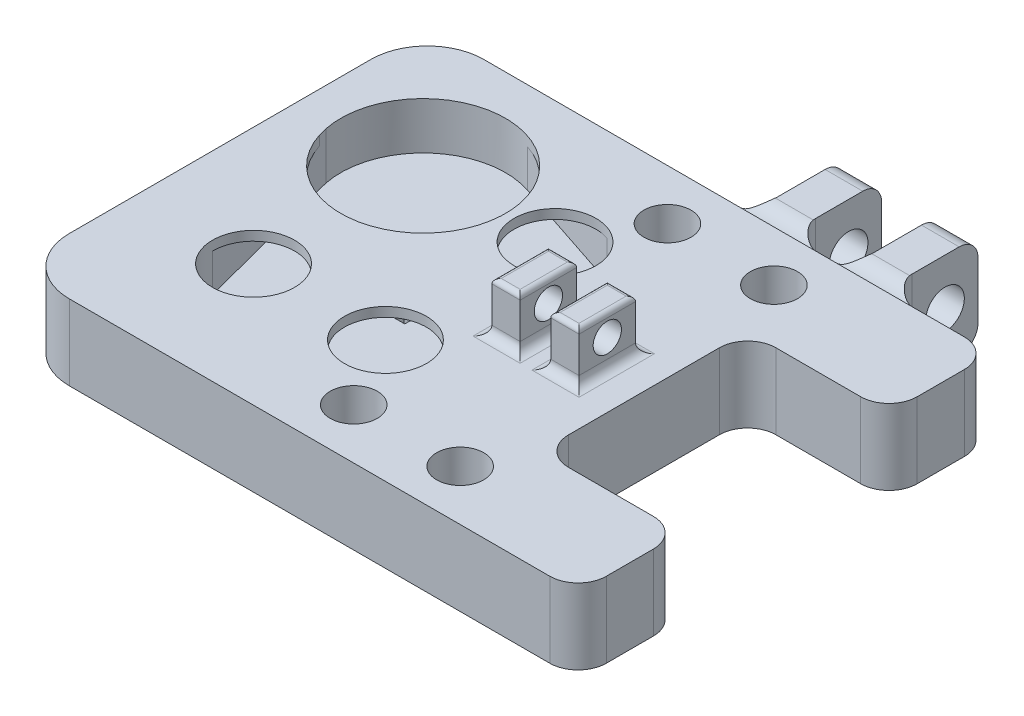
SolidWorks part; units mm, degrees
ref_plane "Front Plane" through (0, 0, 0) normal (0, 0, 1) x (1, 0, 0)
ref_plane "Top Plane" through (0, 0, 0) normal (0, 1, 0) x (1, 0, 0)
ref_plane "Right Plane" through (0, 0, 0) normal (1, 0, 0) x (0, 0, -1)
sketch "Sketch2" plane through (0, 0, 0) normal (0, 1, 0) x (1, 0, 0)
  line L1 (-14.4231, 13.5577) -> (30.5769, 13.5577)
  line L2 (-14.4231, 13.5577) -> (-14.4231, -8.4423)
  line L3 (-14.4231, -8.4423) -> (30.5769, -8.4423)
  line L4 (30.5769, 13.5577) -> (30.5769, -8.4423)
  dimension "D1" = 45
  dimension "D2" = 22
extrude "Boss-Extrude1" add sketch "Sketch2" along normal blind 8
sketch "Sketch3" plane through (0, 0, 0) normal (0, -1, 0) x (1, 0, 0)
  line L0 (30.5769, 8.4423) -> (30.5769, -13.5577) construction
  line L1 (23.5769, -4.0677) -> (3.5769, -4.0677)
  line L2 (23.5769, -4.0677) -> (23.5769, -1.0477)
  line L3 (23.5769, -1.0477) -> (3.5769, -1.0477)
  line L4 (3.5769, -4.0677) -> (3.5769, -1.0477)
  line L5 (-14.4231, -2.5577) -> (30.5769, -2.5577) construction
  line L6 (-14.4231, -13.5577) -> (-14.4231, 8.4423) construction
  dimension "D1" = 20
  dimension "D2" = 7
  dimension "D3" = 3.02
  dimension "D4" = 1.51
extrude "Cut-Extrude1" cut sketch "Sketch3" against normal blind 2
sketch "Sketch4" plane through (0, 0, 0) normal (0, -1, 0) x (1, 0, 0)
  line L0 (3.5769, -1.0477) -> (3.5769, -4.0677) construction
  line L1 (3.5769, -7.5577) -> (-6.4231, -7.5577)
  line L2 (3.5769, -7.5577) -> (3.5769, 2.4423)
  line L3 (3.5769, 2.4423) -> (-6.4231, 2.4423)
  line L4 (-6.4231, -7.5577) -> (-6.4231, -2.5577)
  line L5 (23.5769, -2.5577) -> (-14.4231, -2.5577) construction
  line L7 (23.5769, -4.0677) -> (23.5769, -1.0477) construction
  line L8 (-14.4231, -13.5577) -> (-14.4231, 8.4423) construction
  line L9 (-6.4231, -2.5577) -> (-6.4231, 2.4423)
  dimension "D1" = 10
  dimension "D2" = 10
extrude "Cut-Extrude2" [suppressed] cut sketch "Sketch4" against normal blind 5
sketch "Sketch11" plane through (0, 0, 0) normal (0, -1, 0) x (1, 0, 0)
  circle A0 centre (24.8884, -2.5577) radius 2
  dimension "D1" = 4
extrude "Cut-Extrude4" cut sketch "Sketch11" against normal up to surface (2 mm away) up to face at (13.5769, 2, -2.5577)
sketch "Sketch18" plane through (0, 0, 0) normal (0, -1, 0) x (1, 0, 0)
  line L0 (22.0769, 1.6923) -> (22.0769, -8.4603) construction
  line L4 (30.5769, 8.4423) -> (30.5769, -13.5577) construction
  line L5 (-14.4231, -2.5577) -> (42.1382, -2.5577) construction
  line L6 (-14.4231, -13.5577) -> (-14.4231, 8.4423) construction
  line L7 (2.0769, 1.6923) -> (2.0769, -2.5577) construction
  line L8 (3.3269, -6.8077) -> (3.3269, -2.5577) construction
  circle A0 centre (22.0769, 1.6923) radius 0.6
  circle A1 centre (19.5769, 1.6923) radius 0.6
  circle A2 centre (17.0769, 1.6923) radius 0.6
  circle A3 centre (14.5769, 1.6923) radius 0.6
  circle A4 centre (12.0769, 1.6923) radius 0.6
  circle A5 centre (9.5769, 1.6923) radius 0.6
  circle A6 centre (7.0769, 1.6923) radius 0.6
  circle A7 centre (4.5769, 1.6923) radius 0.6
  circle A8 centre (2.0769, 1.6923) radius 0.6
  circle A9 centre (20.8269, -6.8077) radius 0.6
  circle A10 centre (18.3269, -6.8077) radius 0.6
  circle A11 centre (15.8269, -6.8077) radius 0.6
  circle A12 centre (13.3269, -6.8077) radius 0.6
  circle A13 centre (10.8269, -6.8077) radius 0.6
  circle A14 centre (8.3269, -6.8077) radius 0.6
  circle A15 centre (5.8269, -6.8077) radius 0.6
  circle A16 centre (3.3269, -6.8077) radius 0.6
  dimension "D2" = 1.2
  dimension "D7" = 1.2
  dimension "D3" = 8.5
  dimension "D5" = 1.25
  dimension "D6" = 8.5
  dimension "D1" = 9
  dimension "D8" = 8
sketch "Sketch19" plane through (0, 0, 0) normal (0, -1, 0) x (1, 0, 0)
  line L0 (3.5769, -4.0677) -> (23.5769, -4.0677) construction
  line L5 (3.5769, -1.0477) -> (6.6946, -1.0477)
  line L6 (3.5769, -1.0477) -> (3.5769, -4.0677)
  line L7 (3.5769, -4.0677) -> (6.6946, -4.0677)
  line L8 (6.6946, -1.0477) -> (6.6946, -4.0677)
  dimension "D1" = 3.1177
extrude "Cut-Extrude5" cut sketch "Sketch19" against normal blind 3
sketch "Sketch29" plane through (0, 8, 0) normal (0, 1, 0) x (1, 0, 0)
  line L1 (-14.4231, 13.5577) -> (25.5769, 13.5577)
  line L2 (-14.4231, 13.5577) -> (-14.4231, 24.5577)
  line L3 (-14.4231, 24.5577) -> (25.5769, 24.5577)
  line L4 (25.5769, 13.5577) -> (25.5769, 24.5577)
  line L5 (-14.4231, -8.4423) -> (25.5769, -8.4423)
  line L6 (-14.4231, -8.4423) -> (-14.4231, -19.4423)
  line L7 (-14.4231, -19.4423) -> (25.5769, -19.4423)
  line L8 (25.5769, -8.4423) -> (25.5769, -19.4423)
  dimension "D1" = 40
  dimension "D2" = 11
extrude "Boss-Extrude6" add sketch "Sketch29" against normal up to surface (8 mm away) up to face at (14.4048, 0, -2.5577)
sketch "Sketch21" plane through (0, 3, 0) normal (0, -1, 0) x (1, 0, 0)
  line L0 (3.5769, -2.5577) -> (6.6946, -2.5577) construction
  line L1 (3.5769, -1.0477) -> (3.5769, -4.0677) construction
  line L2 (6.6946, -4.0677) -> (6.6946, -1.0477) construction
  line L3 (5.1358, -1.0477) -> (5.1358, -4.0677) construction
  line L4 (23.5769, -1.0477) -> (3.5769, -1.0477) construction
  line L5 (3.5769, -4.0677) -> (23.5769, -4.0677) construction
  line L6 (19.1358, 15.4423) -> (19.1358, -20.5577)
  line L7 (-10.8642, 15.4423) -> (19.1358, 15.4423)
  line L8 (-10.8642, 15.4423) -> (-10.8642, -20.5577)
  line L9 (-10.8642, -20.5577) -> (19.1358, -20.5577)
  point P12 (5.1358, -2.5577)
  dimension "D1" = 30
  dimension "D2" = 36
  dimension "D3" = 16
extrude "Cut-Extrude8" cut sketch "Sketch21" against normal up to surface (5 mm away) up to face at (16.8269, 8, -2.5577)
sketch "Sketch24" plane through (0, 8, 0) normal (0, 1, 0) x (1, 0, 0)
  line L0 (5.1358, 20.5577) -> (5.1358, -15.4423) construction
  line L1 (-10.8642, -15.4423) -> (-10.8642, 20.5577) construction
  line L3 (-10.8642, 2.5577) -> (21.1358, 2.5577) construction
  line L6 (-1.8642, 11.5577) -> (-1.8642, -6.4423) construction
  line L7 (-10.8642, 20.5577) -> (19.1358, 20.5577)
  line L8 (-10.8642, 20.5577) -> (-10.8642, -15.4423)
  line L9 (-10.8642, -15.4423) -> (19.1358, -15.4423)
  line L10 (19.1358, 20.5577) -> (19.1358, -15.4423)
  line L11 (12.1358, 11.5577) -> (12.1358, -6.4423) construction
  line L13 (12.1358, -6.4423) -> (-1.8642, -6.4423) construction
  line L14 (19.1358, 20.5577) -> (19.1358, -15.4423) construction
  circle A1 centre (12.1358, 11.5577) radius 4.35
  circle A11 centre (-1.8642, 11.5577) radius 8.75
  circle A12 centre (12.1358, -6.4423) radius 4.35
  circle A13 centre (-1.8642, -6.4423) radius 4.35
  point P29 (5.1358, 2.5577)
  dimension "D1" = 8.7
  dimension "D4" = 17.5
  dimension "D2" = 9
  dimension "D3" = 7
  dimension "D5" = 7
  dimension "D6" = 9
  dimension "D7" = 9
  dimension "D8" = 16
extrude "Boss-Extrude3" add sketch "Sketch24" against normal blind 1
sketch "Sketch25" plane through (0, 8, 0) normal (0, 1, 0) x (1, 0, 0)
  line L0 (22.0569, 10.0577) -> (22.0569, -4.9423) construction
  line L1 (20.4319, -0.4423) -> (17.4319, -0.4423)
  line L2 (26.6819, -0.4423) -> (23.6819, -0.4423)
  line L3 (26.6819, -0.4423) -> (26.6819, 5.5577)
  line L4 (26.6819, 5.5577) -> (23.6819, 5.5577)
  line L5 (23.6819, -0.4423) -> (23.6819, 5.5577)
  line L6 (26.6819, -0.4423) -> (23.6819, 5.5577) construction
  line L7 (26.6819, 5.5577) -> (23.6819, -0.4423) construction
  line L8 (20.4319, -0.4423) -> (20.4319, 5.5577)
  line L9 (20.4319, 5.5577) -> (17.4319, 5.5577)
  line L10 (17.4319, -0.4423) -> (17.4319, 5.5577)
  line L11 (20.4319, -0.4423) -> (17.4319, 5.5577) construction
  line L12 (20.4319, 5.5577) -> (17.4319, -0.4423) construction
  line L13 (-14.4231, 2.5577) -> (30.5769, 2.5577) construction
  line L14 (-14.4231, 24.5577) -> (-14.4231, -19.4423) construction
  line L15 (30.5769, -8.4423) -> (30.5769, 13.5577) construction
  circle A0 centre (22.0569, 2.5577) radius 6.2555
  circle A1 centre (22.0569, 2.5577) radius 5.8
  point P6 (22.0569, 2.5577)
  point P7 (25.1819, 2.5577)
  point P16 (18.9319, 2.5577)
  dimension "D1" = 15
  dimension "D2" = 3
  dimension "D3" = 6
  dimension "D4" = 3.125
  dimension "D5" = 3.125
  dimension "D6" = 6
  dimension "D7" = 3
  dimension "D8" = 8.52
extrude "Boss-Extrude4" add sketch "Sketch25" along normal blind 5.3 contours L10 L1 L8 L9 | L5 L2 L3 L4 region at (18.9319, 8, -2.5577) region at (25.1819, 8, -2.5577)
sketch "Sketch26" plane through (26.6819, 0, 0) normal (1, 0, 0) x (0, 0, -1)
  line L0 (2.5577, 13.3) -> (2.5577, 8) construction
  line L1 (-0.4423, 13.3) -> (5.5577, 13.3) construction
  line L2 (-8.4423, 8) -> (13.5577, 8) construction
  line L3 (-0.4423, 8) -> (5.5577, 8) construction
  circle A0 centre (2.5577, 11) radius 1.5
  dimension "D1" = 3
  dimension "D2" = 3
extrude "Cut-Extrude9" cut sketch "Sketch26" against normal up to surface (9.25 mm away) up to face at (17.4319, 10.65, -2.5577)
fillet "Fillet2" radius 1 8 edges at (25.1819, 8, -5.5577) (18.9319, 8, -5.5577) (23.6819, 8, -2.5577) (17.4319, 8, -2.5577) (26.6819, 8, -2.5577) (25.1819, 8, 0.4423) (18.9319, 8, 0.4423) (20.4319, 8, -2.5577)
fillet "Fillet3" radius 0.5 8 edges at (18.9319, 13.3, 0.4423) (20.4319, 13.3, -2.5577) (17.4319, 13.3, -2.5577) (18.9319, 13.3, -5.5577) (25.1819, 13.3, -5.5577) (25.1819, 13.3, 0.4423) (23.6819, 13.3, -2.5577) (26.6819, 13.3, -2.5577)
sketch "Sketch27" plane through (0, 8, 0) normal (0, 1, 0) x (1, 0, 0)
  line L0 (30.5769, 13.5577) -> (25.5769, 13.5577) construction
  line L1 (25.5769, 13.5577) -> (45.5769, 13.5577)
  line L2 (25.5769, 13.5577) -> (25.5769, 24.5577)
  line L3 (25.5769, 24.5577) -> (45.5769, 24.5577)
  line L4 (45.5769, 13.5577) -> (45.5769, 24.5577)
  line L5 (25.5769, 13.5577) -> (25.5769, 24.5577) construction
  dimension "D1" = 20
  dimension "D2" = 11
extrude "Boss-Extrude5" add sketch "Sketch27" against normal up to surface (8 mm away) up to face at (14.4048, 0, -2.5577)
sketch "Sketch28" plane through (0, 8, 0) normal (0, 1, 0) x (1, 0, 0)
  line L0 (16.4169, 19.2077) -> (27.7169, 19.2077) construction
  line L1 (30.5769, -8.4423) -> (30.5769, 13.5577) construction
  line L4 (-14.4231, 24.5577) -> (-14.4231, -19.4423) construction
  circle A0 centre (16.4169, 19.2077) radius 2.5
  circle A1 centre (27.7169, 19.2077) radius 2.5
  point P2 (-14.4231, 2.5577)
  dimension "D1" = 11.3
  dimension "D2" = 5
  dimension "D3" = 16.65
  dimension "D4" = 2.86
extrude "Cut-Extrude10" cut sketch "Sketch28" against normal up to next
ref_plane "Plane1" through (0, 0, -2.5577) normal (0, 0, 1) x (1, 0, 0)
mirror "Mirror1" about plane through (0, 0, -2.5577) normal (0, 0, 1) of "Cut-Extrude10", "Boss-Extrude5"
fillet "Fillet5" radius 6 2 edges at (-14.4231, 4, -24.5577) (-14.4231, 4, 19.4423)
fillet "Fillet6" radius 3 6 edges at (30.5769, 4, 8.4423) (45.5769, 4, -13.5577) (30.5769, 4, -13.5577) (45.5769, 4, 8.4423) (45.5769, 4, -24.5577) (45.5769, 4, 19.4423)
sketch "Sketch30" plane through (0, 8, 0) normal (0, 1, 0) x (1, 0, 0)
  line L4 (19.4085, 23.1759) -> (19.4085, -18.1335)
  line L5 (19.4085, -18.1335) -> (-11.192, -18.1335)
  line L6 (-11.192, -18.1335) -> (-11.192, 23.1759)
  line L7 (-11.192, 23.1759) -> (19.4085, 23.1759)
  line L8 (-1.8642, -10.7923) -> (12.1358, -10.7923)
  line L9 (16.4858, -6.4423) -> (16.4858, 11.5577)
  line L10 (-10.4422, 9.831) -> (-6.2142, -6.4423)
  line L11 (0.8858, 19.8643) -> (13.5029, 15.6873)
  circle A0 centre (16.4169, -14.0923) radius 2.5
  circle A1 centre (16.4169, 19.2077) radius 2.5
  circle A8 centre (-1.8642, -6.4423) radius 4.35 construction
  circle A9 centre (12.1358, -6.4423) radius 4.35 construction
  circle A10 centre (12.1358, 11.5577) radius 4.35 construction
  circle A11 centre (-1.8642, 11.5577) radius 8.75 construction
  arc A12 (0.8858, 19.8643) -> (-10.4422, 9.831) centre (-1.8642, 11.5577) ccw
  arc A13 (16.4858, 11.5577) -> (13.5029, 15.6873) centre (12.1358, 11.5577) ccw
  arc A14 (16.4858, -6.4423) -> (12.1358, -10.7923) centre (12.1358, -6.4423) cw
  arc A15 (-1.8642, -10.7923) -> (-6.2142, -6.4423) centre (-1.8642, -6.4423) cw
extrude "Boss-Extrude7" add sketch "Sketch30" against normal up to surface (5 mm away) up to face at (5.1358, 3, -2.5577)
sketch "Sketch32" plane through (0, 0, -24.5577) normal (0, 0, -1) x (-1, 0, 0)
  line L0 (-42.5769, 4) -> (-13.0541, 4) construction
  line L1 (-20.7971, 9) -> (-24.7971, 9)
  line L2 (-20.7971, 9) -> (-20.7971, -1)
  line L3 (-20.7971, -1) -> (-24.7971, -1)
  line L4 (-24.7971, 9) -> (-24.7971, -1)
  line L5 (-20.7971, 9) -> (-24.7971, -1) construction
  line L6 (-20.7971, -1) -> (-24.7971, 9) construction
  line L7 (-31.0271, 9) -> (-35.0271, 9)
  line L8 (-31.0271, 9) -> (-31.0271, -1)
  line L9 (-31.0271, -1) -> (-35.0271, -1)
  line L10 (-35.0271, 9) -> (-35.0271, -1)
  line L11 (-31.0271, 9) -> (-35.0271, -1) construction
  line L12 (-31.0271, -1) -> (-35.0271, 9) construction
  line L13 (-42.5769, 8) -> (-42.5769, 0) construction
  point P0 (-22.7971, 4)
  point P5 (-33.0271, 4)
  point P14 (0, 0)
  point P15 (0, 0)
  dimension "D1" = 4
  dimension "D2" = 10
  dimension "D3" = 4
  dimension "D4" = 10
  dimension "D5" = 6.23
extrude "Boss-Extrude8" add sketch "Sketch32" along normal blind 9
sketch "Sketch34" plane through (20.7971, 0, 0) normal (-1, 0, 0) x (0, 0, 1)
  line L0 (-33.5577, -1) -> (-24.5577, -1) construction
  line L1 (-33.5577, -1) -> (-33.5577, 9) construction
  circle A0 centre (-30.0577, 4) radius 2.05
  point P2 (0, 0)
  dimension "D1" = 5
  dimension "D2" = 3.5
  dimension "D3" = 4.1
extrude "Cut-Extrude11" cut sketch "Sketch34" against normal through all both and the other way through all
fillet "Fillet7" radius 2 8 edges at (33.0271, -1, -24.5577) (33.0271, -1, -33.5577) (33.0271, 9, -24.5577) (33.0271, 9, -33.5577) (22.7971, 9, -24.5577) (22.7971, 9, -33.5577) (22.7971, -1, -24.5577) (22.7971, -1, -33.5577)
fillet "Fillet8" radius 2 4 edges at (20.7971, 4, -24.5577) (24.7971, 4, -24.5577) (31.0271, 4, -24.5577) (35.0271, 4, -24.5577)
